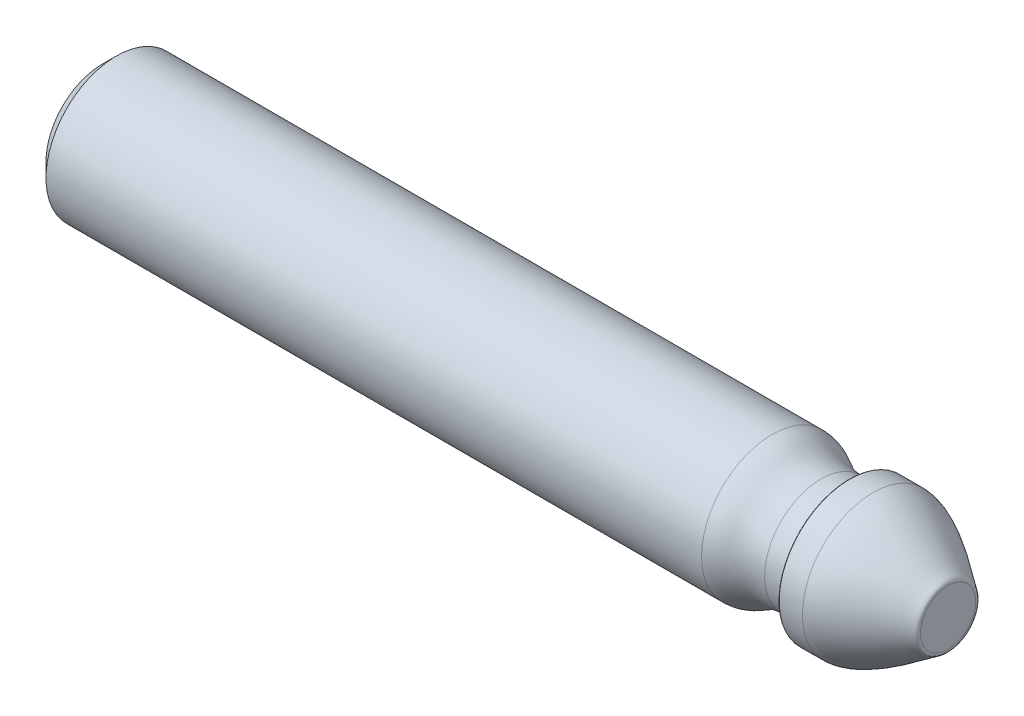
SolidWorks part; units mm, degrees
material "Alloy Steel"
ref_plane "Front" through (0, 0, 0) normal (0, 0, 1) x (1, 0, 0)
ref_plane "Top" through (0, 0, 0) normal (0, 1, 0) x (1, 0, 0)
ref_plane "Right" through (0, 0, 0) normal (1, 0, 0) x (0, 0, -1)
sketch "Sketch1" plane through (0, 0, 0) normal (0, 0, 1) x (1, 0, 0)
  line L0 (-19.05, 0) -> (19.05, 0) construction
  line L1 (19.05, 3.175) -> (19.05, -3.175) construction
  line L2 (-19.05, 3.175) -> (-19.05, -3.175) construction
  dimension "Length" = 38.1
  dimension "Diameter" = 6.35
sketch "Sketch2" plane through (0, 0, 0) normal (1, 0, 0) x (0, 0, -1)
  circle A0 centre (0, 0) radius 3.175
extrude "Extrude1" add sketch "Sketch2" against normal up to vertex (19.05 mm away) and the other way up to vertex (19.05 mm away) up to point (-19.05, 3.175, 0) other way up to point (19.05, 3.175, 0)
chamfer "Chamfer1" distance 0.635 angle 45 2 edges at (19.05, 0, -3.175) (-19.05, 0, -3.175)
sketch "Sketch3" plane through (0, 0, 0) normal (0, 0, 1) x (1, 0, 0)
  line L0 (-19.05, 0) -> (19.05, 0) construction
  line L1 (-19.05, 2.54) -> (-19.05, -2.54) construction
  line L2 (19.05, -2.54) -> (19.05, 2.54) construction
  line L3 (18.415, 3.175) -> (-18.415, 3.175) construction
  line L4 (15.6622, 3.175) -> (14.5934, 3.175)
  line L5 (16.629, 3.175) -> (14.655, 3.175) construction
  line L6 (19.05, 0.802) -> (19.05, 1.6965) construction
  line L7 (19.05, 1.2434) -> (19.05, 3.175)
  line L8 (19.05, 3.175) -> (15.6622, 3.175)
  line L9 (14.5934, 3.175) -> (14.5934, 2.54)
  line L10 (14.5934, 2.54) -> (13.3234, 2.54)
  line L11 (11.1187, 3.175) -> (14.5934, 3.175)
  line L12 (11.6265, 3.175) -> (9.464, 3.175) construction
  line L13 (14.3233, 2.54) -> (12.3233, 2.54) construction
  line L14 (11.1187, 3.175) -> (14.5934, 3.175)
  spline S0 degree 3 poles (15.6622, 3.175) (16.6428, 3.175) (18.614, 1.6311) (19.0441, 1.3825) (19.05, 1.3487) (19.05, 1.2434) knots 0 0 0 0 0.565725 0.665725 1 1 1 1
  spline S1 degree 3 poles (11.1187, 3.175) (11.9879, 3.175) (12.0734, 2.54) (13.3234, 2.54) knots 0 0 0 0 1 1 1 1
revolve "Cut-Revolve1" cut sketch "Sketch3" angle 360 about L0 region at (13.3125, 2.889, 0) region at (18.092, 2.592, 0)
fillet "Fillet1" radius 0.0254 1 edges at (14.5934, 0, 3.175)
sketch "minimum_diameter" plane through (19.05, 0, 0) normal (1, 0, 0) x (0, 0, -1)
  circle A0 centre (0, 0) radius 2.54 construction
  circle A1 centre (0, 0) radius 2.54 construction
equation "\"D1@Chamfer1\" = \"Diameter@Sketch1\"*.1"
